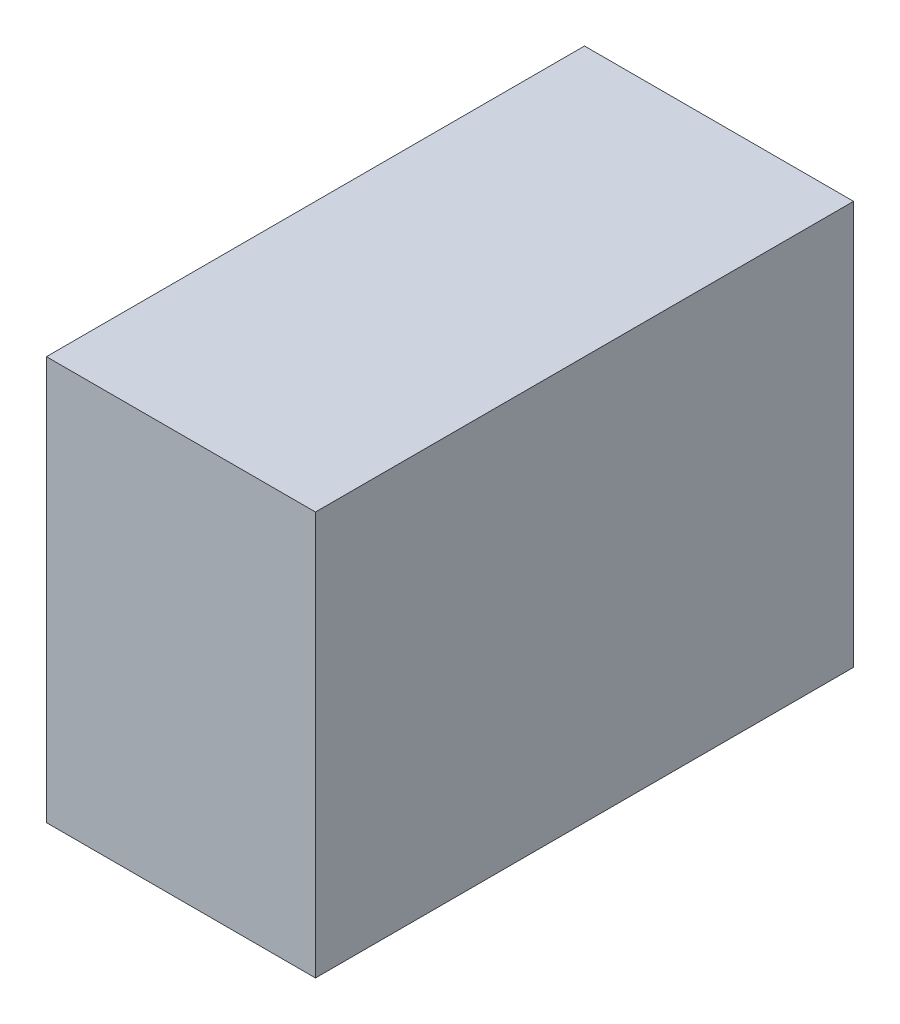
SolidWorks part; units mm, degrees
ref_plane "Front Plane" through (0, 0, 0) normal (0, 0, 1) x (1, 0, 0)
ref_plane "Top Plane" through (0, 0, 0) normal (0, 1, 0) x (1, 0, 0)
ref_plane "Right Plane" through (0, 0, 0) normal (1, 0, 0) x (0, 0, -1)
sketch "Sketch1" plane through (0, 0, 0) normal (0, 1, 0) x (1, 0, 0)
  circle A0 centre (0, 0) radius 2.5
  dimension "D1" = 5
extrude "Boss-Extrude1" add sketch "Sketch1" along normal blind 5
sketch "Sketch2" plane through (0, 5, 0) normal (0, 1, 0) x (1, 0, 0)
  line L1 (15, 15) -> (-15, 15)
  line L2 (15, 15) -> (15, -45)
  line L3 (15, -45) -> (-15, -45)
  line L4 (-15, 15) -> (-15, -45)
  circle A0 centre (0, 0) radius 2.5 construction
  dimension "D4" = 15
  dimension "D1" = 60
  dimension "D2" = 30
  dimension "D3" = 15
extrude "Boss-Extrude2" add sketch "Sketch2" along normal blind 45
ref_axis "Axis1" through (0, 0, 0) along (0, -1, 0)
